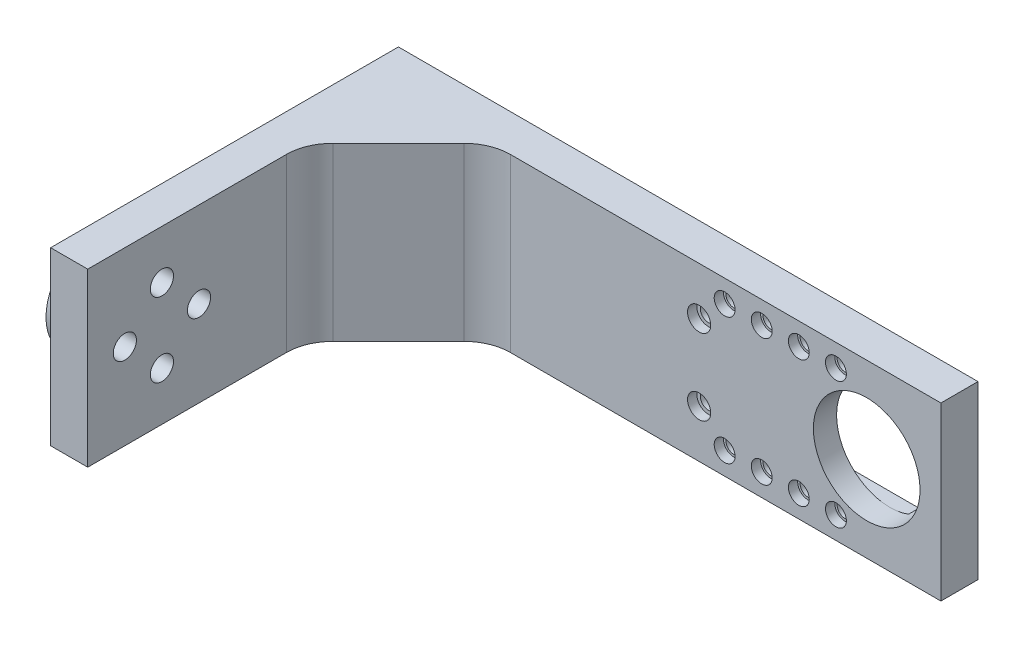
SolidWorks part; units mm, degrees
ref_plane "Front Plane" through (0, 0, 0) normal (0, 0, 1) x (1, 0, 0)
ref_plane "Top Plane" through (0, 0, 0) normal (0, 1, 0) x (1, 0, 0)
ref_plane "Right Plane" through (0, 0, 0) normal (1, 0, 0) x (0, 0, -1)
sketch "Sketch1" plane through (0, 0, 0) normal (0, 1, 0) x (1, 0, 0)
  line L0 (0, 0) -> (0, 75)
  line L1 (0, 75) -> (125, 75)
  line L2 (125, 75) -> (125, 67)
  line L3 (125, 67) -> (8, 67)
  line L4 (8, 67) -> (8, 0)
  line L5 (8, 0) -> (0, 0)
  dimension "D1" = 117
  dimension "D2" = 125
  dimension "D3" = 8
  dimension "D4" = 67
  dimension "D5" = 75
extrude "Boss-Extrude1" add sketch "Sketch1" along normal blind 37
sketch "Sketch2" plane through (0, 0, -75) normal (0, 0, -1) x (-1, 0, 0)
  line L0 (-125, 18.5) -> (-109, 18.5)
  line L1 (-125, 37) -> (-125, 0) construction
  circle A0 centre (-109, 18.5) radius 11.5
  dimension "D2" = 23
  dimension "D1" = 16
extrude "Cut-Extrude1" cut sketch "Sketch2" against normal up to next contours A0 region at (109, 7.3253, -75)
sketch "Sketch3" plane through (0, 0, -75) normal (0, 0, -1) x (-1, 0, 0)
  line L0 (-125, 32.19) -> (-102.36, 32.19)
  line L1 (-125, 37) -> (-125, 0) construction
  line L2 (-102.36, 32.19) -> (-102.36, 37)
  line L3 (-125, 37) -> (0, 37) construction
  line L4 (-125, 18.5) -> (-57.038, 18.5)
  circle A0 centre (-102.36, 32.19) radius 1.75
  circle A1 centre (-94.36, 32.19) radius 1.75
  circle A2 centre (-86.36, 32.19) radius 1.75
  circle A3 centre (-78.36, 32.19) radius 1.75
  circle A4 centre (-78.36, 4.81) radius 1.75
  circle A5 centre (-86.36, 4.81) radius 1.75
  circle A6 centre (-94.36, 4.81) radius 1.75
  circle A7 centre (-102.36, 4.81) radius 1.75
  dimension "D3" = 3.5
  dimension "D1" = 22.64
  dimension "D2" = 4.81
  dimension "D4" = 4
extrude "Cut-Extrude2" cut sketch "Sketch3" against normal up to next contours A5 | A7 | A6 | A4 | A3 | A2 | A1 | A0 region at (86.36, 4.81, -75)
sketch "Sketch4" plane through (0, 0, -75) normal (0, 0, -1) x (-1, 0, 0)
  line L0 (-113, 30) -> (-113, 7)
  line L4 (-113, 30) -> (-75, 30)
  line L5 (-75, 30) -> (-75, 7)
  line L6 (-75, 7) -> (-113, 7)
  dimension "D3" = 23
  dimension "D4" = 38
  dimension "D5" = 38
sketch "Sketch5" plane through (0, 0, 0) normal (-1, 0, 0) x (0, 0, 1)
  circle A1 centre (-16, 10.5) radius 1.75
  circle A2 centre (-24, 18.5) radius 1.75
  circle A3 centre (-16, 26.5) radius 1.75
  circle A4 centre (-8, 18.5) radius 1.75
  point P13 (-16, 18.5)
  dimension "D4" = 3.5
  dimension "D1" = 4
extrude "Cut-Extrude5" cut sketch "Sketch5" against normal up to next
sketch "Sketch6" plane through (0, 0, 0) normal (-1, 0, 0) x (0, 0, 1)
  line L0 (0, 18.5) -> (-16, 18.5)
  line L1 (0, 37) -> (0, 0) construction
  circle A0 centre (-16, 18.5) radius 11
  circle A1 centre (-16, 10.5) radius 1.75 construction
  circle A2 centre (-24, 18.5) radius 1.75 construction
  circle A3 centre (-16, 26.5) radius 1.75 construction
  circle A4 centre (-8, 18.5) radius 1.75 construction
  circle A5 centre (-16, 10.5) radius 1.75
  circle A6 centre (-24, 18.5) radius 1.75
  circle A7 centre (-16, 26.5) radius 1.75
  circle A8 centre (-8, 18.5) radius 1.75
  circle M1 centre (-8, 18.5) radius 1.75
  circle M2 centre (-16, 26.5) radius 1.75
  circle M3 centre (-24, 18.5) radius 1.75
  circle M4 centre (-16, 10.5) radius 1.75
  dimension "D2" = 22
  dimension "D1" = 16
extrude "Boss-Extrude3" add sketch "Sketch6" along normal blind 6 contours A0 M1 M3 M4 M2 region at (0, 18.5, -26.6889)
extrude "Cut-Extrude6" cut sketch "Sketch4" against normal blind 3
sketch "Sketch7" plane through (75, 0, 0) normal (1, 0, 0) x (0, 0, -1)
  line L4 (75, 7) -> (75, 30)
  line L5 (75, 30) -> (72, 30)
  line L6 (72, 30) -> (72, 7)
  line L7 (72, 7) -> (75, 7)
  line L8 (75, 7) -> (75, 30)
  line L9 (75, 30) -> (72, 30)
  line L10 (72, 30) -> (72, 7)
  line L11 (72, 7) -> (75, 7)
  dimension "D1" = 0
sketch "Sketch9" plane through (0, 0, -67) normal (0, 0, 1) x (1, 0, 0)
  circle A1 centre (78.36, 32.19) radius 2.25
  circle A2 centre (86.36, 32.19) radius 2.25
  circle A3 centre (94.36, 32.19) radius 2.25
  circle A4 centre (102.36, 32.19) radius 2.25
  circle A6 centre (78.36, 4.81) radius 2.25
  circle A7 centre (86.36, 4.81) radius 2.25
  circle A8 centre (94.36, 4.81) radius 2.25
  circle A9 centre (102.36, 4.81) radius 2.25
  dimension "D2" = 4.5
  dimension "D3" = 4.5
  dimension "D4" = 4.5
  dimension "D5" = 4.5
  dimension "D7" = 4.5
  dimension "D8" = 4.5
  dimension "D9" = 4.5
  dimension "D10" = 4.5
extrude "Cut-Extrude8" cut sketch "Sketch9" against normal blind 2
sketch "Sketch10" plane through (8, 0, 0) normal (1, 0, 0) x (0, 0, -1)
  circle A0 centre (24, 18.5) radius 2.5
  circle A1 centre (16, 10.5) radius 2.5
  circle A2 centre (8, 18.5) radius 2.5
  circle A3 centre (16, 26.5) radius 2.5
  dimension "D1" = 5
  dimension "D2" = 5
  dimension "D3" = 5
  dimension "D4" = 5
extrude "Cut-Extrude9" cut sketch "Sketch10" against normal blind 6
chamfer "Chamfer1" distance 20 angle 45 1 edges at (8, 18.5, -67)
fillet "Fillet5" radius 10 2 edges at (8, 18.5, -47) (28, 18.5, -67)
sketch "Sketch11" plane through (0, 0, -67) normal (0, 0, 1) x (1, 0, 0)
  line L0 (78.36, 4.81) -> (72.86, 4.81)
  line L1 (72.86, 4.81) -> (72.86, 10.31)
  line L2 (32.1421, 18.5) -> (74.9862, 18.5)
  line L3 (32.1421, 37) -> (32.1421, 0) construction
  circle A0 centre (72.86, 10.31) radius 1.75
  circle A1 centre (72.86, 26.69) radius 1.75
  dimension "D3" = 3.5
  dimension "D1" = 5.5
  dimension "D2" = 5.5
extrude "Cut-Extrude10" cut sketch "Sketch11" against normal up to next contours A0 | A1 region at (74.0624, 9.1076, -67) region at (72.86, 26.69, -67)
sketch "Sketch12" plane through (0, 0, -67) normal (0, 0, 1) x (1, 0, 0)
  circle A0 centre (72.86, 10.31) radius 2.5
  circle A1 centre (72.86, 26.69) radius 2.5
  dimension "D1" = 5
  dimension "D2" = 5
extrude "Cut-Extrude11" cut sketch "Sketch12" against normal blind 2
extrude "Boss-Extrude4" add sketch "Sketch7" along normal blind 0.5
